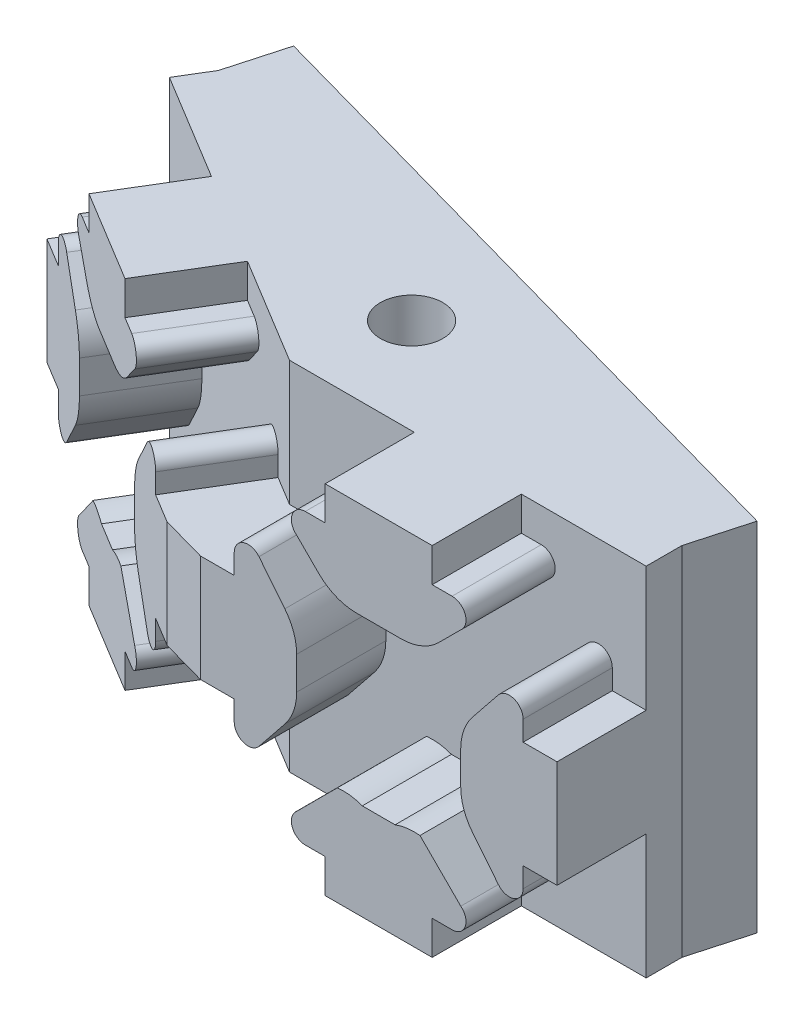
SolidWorks part; units mm, degrees
ref_plane "Ebene vorne" through (0, 0, 0) normal (0, 0, 1) x (1, 0, 0)
ref_plane "Ebene oben" through (0, 0, 0) normal (0, 1, 0) x (1, 0, 0)
ref_plane "Ebene rechts" through (0, 0, 0) normal (1, 0, 0) x (0, 0, -1)
sketch "Skizze1" plane through (0, 0, 0) normal (0, 0, 1) x (1, 0, 0)
  line L1 (0, 0) -> (20, 0)
  line L2 (0, 0) -> (0, 20)
  line L3 (0, 20) -> (20, 20)
  line L4 (20, 0) -> (20, 20)
  dimension "D1" = 20
extrude "Aufsatz-Linear austragen1" add sketch "Skizze1" along normal blind 2
sketch "Skizze2" plane through (0, 0, 2) normal (0, 0, 1) x (1, 0, 0)
  line L0 (10, 20) -> (10, 0) construction
  line L1 (20, 20) -> (0, 20) construction
  line L2 (0, 0) -> (20, 0) construction
  line L3 (0, 10) -> (20, 10) construction
  line L4 (0, 20) -> (0, 0) construction
  line L5 (20, 0) -> (20, 20) construction
  line L6 (13, 20) -> (7, 20)
  line L7 (13, 20) -> (13, 18.1)
  line L8 (13, 18.1) -> (14.1169, 18.1)
  line L9 (14.6053, 16.7118) -> (12.4935, 14.6)
  line L10 (5.3947, 16.7118) -> (7.5065, 14.6)
  line L11 (12.4935, 14.6) -> (7.5065, 14.6)
  line L12 (7, 18.1) -> (5.8831, 18.1)
  line L13 (7, 20) -> (7, 18.1)
  line L14 (10, 10) -> (20, 20) construction
  line L15 (20, 7) -> (18.1, 7)
  line L16 (18.1, 7) -> (18.1, 5.8831)
  line L17 (14.6, 10.9198) -> (14.6, 9.0802)
  line L18 (16.7118, 5.3947) -> (15.2607, 7.202)
  line L19 (16.7118, 14.6053) -> (15.2607, 12.798)
  line L20 (18.1, 13) -> (18.1, 14.1169)
  line L21 (20, 13) -> (18.1, 13)
  line L22 (20, 13) -> (20, 7)
  line L23 (7, 0) -> (7, 1.9)
  line L24 (7, 1.9) -> (5.8831, 1.9)
  line L25 (10.9198, 5.4) -> (9.0802, 5.4)
  line L26 (5.3947, 3.2882) -> (7.6845, 5.578)
  line L27 (14.6053, 3.2882) -> (12.3155, 5.578)
  line L28 (13, 1.9) -> (14.1169, 1.9)
  line L29 (13, 0) -> (13, 1.9)
  line L30 (13, 0) -> (7, 0)
  line L31 (0, 13) -> (0, 7)
  line L32 (0, 13) -> (1.9, 13)
  line L33 (1.9, 13) -> (1.9, 14.1169)
  line L34 (3.2882, 14.6053) -> (4.7393, 12.798)
  line L35 (3.2882, 5.3947) -> (4.7393, 7.202)
  line L36 (5.4, 10.9198) -> (5.4, 9.0802)
  line L37 (1.9, 7) -> (1.9, 5.8831)
  line L38 (0, 7) -> (1.9, 7)
  line L39 (10, 10) -> (0, 20) construction
  line L40 (9.0802, 14.6) -> (10.9198, 14.6)
  circle A0 centre (10, 10) radius 2.1
  arc A1 (1.9, 14.1169) -> (3.2882, 14.6053) centre (2.68, 14.1169) cw
  arc A2 (1.9, 5.8831) -> (3.2882, 5.3947) centre (2.68, 5.8831) ccw
  arc A3 (5.8831, 18.1) -> (5.3947, 16.7118) centre (5.8831, 17.32) ccw
  arc A4 (14.1169, 18.1) -> (14.6053, 16.7118) centre (14.1169, 17.32) cw
  arc A5 (18.1, 14.1169) -> (16.7118, 14.6053) centre (17.32, 14.1169) ccw
  arc A6 (18.1, 5.8831) -> (16.7118, 5.3947) centre (17.32, 5.8831) cw
  arc A7 (14.1169, 1.9) -> (14.6053, 3.2882) centre (14.1169, 2.68) ccw
  arc A8 (5.8831, 1.9) -> (5.3947, 3.2882) centre (5.8831, 2.68) cw
  arc A9 (4.7393, 12.798) -> (5.4, 10.9198) centre (2.4, 10.9198) cw
  arc A10 (4.7393, 7.202) -> (5.4, 9.0802) centre (2.4, 9.0802) ccw
  arc A13 (15.2607, 7.202) -> (14.6, 9.0802) centre (17.6, 9.0802) cw
  arc A14 (15.2607, 12.798) -> (14.6, 10.9198) centre (17.6, 10.9198) ccw
  arc A15 (7.6845, 5.578) -> (9.0802, 5.4) centre (8.0135, 2.5961) cw
  arc A16 (12.3155, 5.578) -> (10.9198, 5.4) centre (11.9865, 2.5961) ccw
  point P18 (10, 14.6)
  point P33 (14.6, 10)
  point P42 (10, 5.4)
  point P51 (5.4, 10)
  line M39 (0, 20) -> (0, 0)
  line M40 (0, 0) -> (20, 0)
  line M41 (20, 0) -> (20, 20)
  line M42 (20, 20) -> (0, 20)
  dimension "D1" = 4.2
  dimension "D6" = 0.78
  dimension "D4" = 3
  dimension "D2" = 6
  dimension "D3" = 1.9
  dimension "D5" = 45
  dimension "D7" = 5.4
  dimension "D8" = 5.4
extrude "Aufsatz-Linear austragen3" add sketch "Skizze2" along normal blind 5 contours A4 L8 L7 L13 L12 A3 L10 L11 L9 M42 | L35 A10 L36 A9 L34 A1 L33 L32 L38 L37 A2 M39 | L27 A16 L25 A15 L26 A8 L24 L23 L29 L28 A7 M40 | L19 A14 L17 A13 L18 A6 L16 L15 L21 L20 A5 M41 region at (10, 17.2545, 2) region at (17.3263, 10, 2) region at (2.6737, 10, 2) region at (10, 2.7754, 2)
fillet "Verrundung1" radius 3 2 edges at (12.4935, 14.6, 4.5) (7.5065, 14.6, 4.5)
ref_plane "Ebene1" through (0.5184, 0, 0.1449) normal (-0.9631, 0, -0.2691) x (-0.2691, 0, 0.9631)
mirror "Spiegeln1" about plane through (0.5184, 0, 0.1449) normal (-0.9631, 0, -0.2691) of "Verrundung1", "Aufsatz-Linear austragen3", "Aufsatz-Linear austragen1"
ref_plane "Ebene2" through (1.4486, 0, -5.1839) normal (0.2691, 0, -0.9631) x (-0.9631, 0, -0.2691)
ref_plane "Ebene3" through (2.3699, 0, -8.4809) normal (0.2691, 0, -0.9631) x (-0.9631, 0, -0.2691)
sketch "Skizze3" plane through (2.3699, 0, -8.4809) normal (0.2691, 0, -0.9631) x (-0.9631, 0, -0.2691)
  line L0 (-19.2621, 20) -> (-19.2621, 0)
  line L1 (-19.2621, 0) -> (18.1856, 0)
  line L2 (18.1856, 0) -> (18.1856, 20)
  line L3 (18.1856, 20) -> (-19.2621, 20)
extrude "Aufsatz-Linear austragen4" add sketch "Skizze3" against normal up to next
sketch "Skizze4" plane through (0, 0, 0) normal (0, -1, 0) x (1, 0, 0)
  line L0 (0, 2) -> (2.8883, -8.3361) construction
  line L1 (20.9213, -3.297) -> (-15.1448, -13.3752) construction
  circle A0 centre (1.4953, -3.3513) radius 1.75
  circle A1 centre (1.4953, -3.3513) radius 2.9
  dimension "D1" = 3.5
  dimension "D2" = 5.8
extrude "Schnitt-Linear austragen1" cut sketch "Skizze4" against normal through all contours A0 L0 | L0 A0 region at (2.2107, 0, -3.1514) region at (0.78, 0, -3.5512)
extrude "Schnitt-Linear austragen2" cut sketch "Skizze4<3>" against normal offset from surface (16 mm away) 4 up to face at (1.4953, 20, -5.1013)
sketch "Skizze4<3>" plane through (0, 0, 0) normal (0, -1, 0) x (1, 0, 0) same geometry as "Skizze4"
ref_plane "Ebene4" through (-1.8144, 0, 6.493) normal (-0.2691, 0, 0.9631) x (0.9631, 0, 0.2691)
sketch "Skizze5" plane through (-1.8144, 0, 6.493) normal (-0.2691, 0, 0.9631) x (0.9631, 0, 0.2691)
  line L0 (-0.8074, 13) -> (1.8839, 13)
  line L1 (1.8839, 13) -> (1.8839, 7)
  line L2 (1.8839, 7) -> (-0.8074, 7)
  line L3 (-0.8074, 7) -> (-0.8074, 13)
extrude "Aufsatz-Linear austragen5" add sketch "Skizze5" against normal up to next
